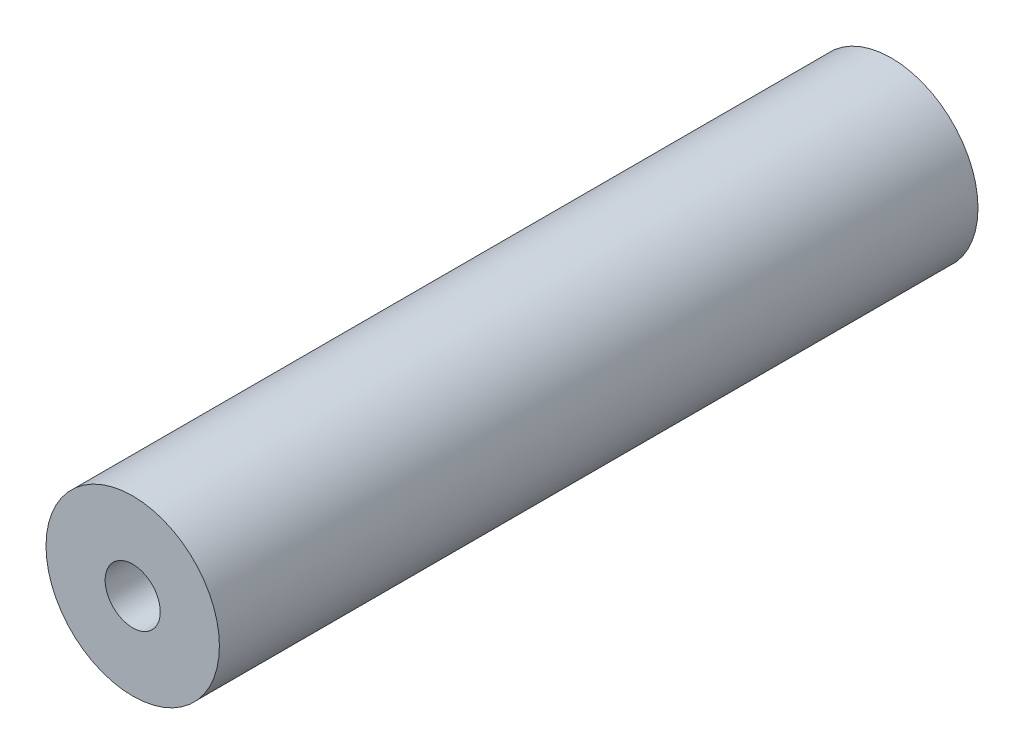
SolidWorks part; units mm, degrees
ref_plane "Front Plane" through (0, 0, 0) normal (0, 0, 1) x (1, 0, 0)
ref_plane "Top Plane" through (0, 0, 0) normal (0, 1, 0) x (1, 0, 0)
ref_plane "Right Plane" through (0, 0, 0) normal (1, 0, 0) x (0, 0, -1)
sketch "Sketch1" plane through (0, 0, 0) normal (0, 0, 1) x (1, 0, 0)
  circle A1 centre (0, 0) radius 6.35
  circle A2 centre (0, 0) radius 2.0193
  dimension "D2" = 12.7
  dimension "D3" = 4.0386
extrude "Boss-Extrude1" add sketch "Sketch1" along normal mid plane 55.5625 contours A1 A2 region at (-6.1704, 0, 0)
